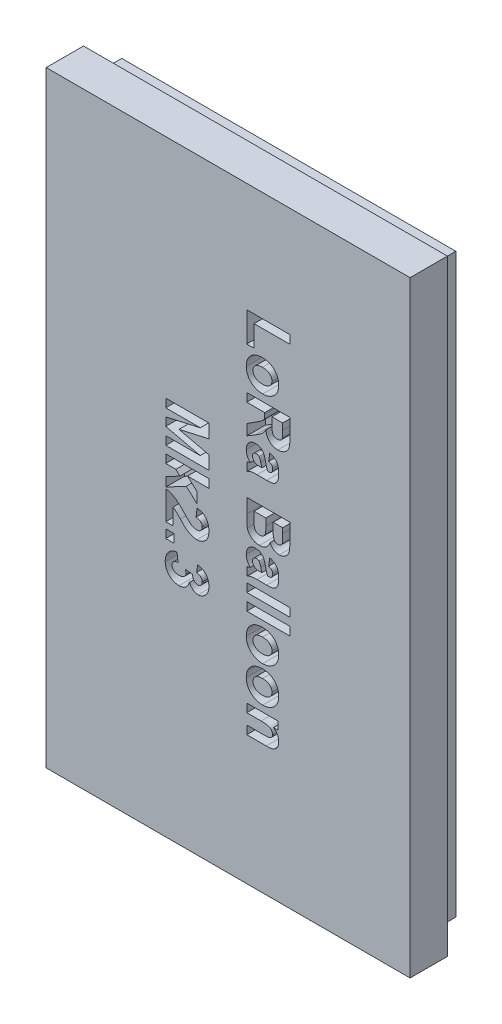
SolidWorks part; units mm, degrees
ref_plane "Front Plane" through (0, 0, 0) normal (0, 0, 1) x (1, 0, 0)
ref_plane "Top Plane" through (0, 0, 0) normal (0, 1, 0) x (1, 0, 0)
ref_plane "Right Plane" through (0, 0, 0) normal (1, 0, 0) x (0, 0, -1)
sketch "Sketch1" plane through (0, 0, 0) normal (0, 0, 1) x (1, 0, 0)
  line L1 (0, 0) -> (39, 0)
  line L2 (0, 0) -> (0, 65)
  line L3 (0, 65) -> (39, 65)
  line L4 (39, 0) -> (39, 65)
  dimension "D1" = 65
  dimension "D2" = 39
extrude "Base" add sketch "Sketch1" along normal blind 4
sketch "Sketch2" plane through (0, 0, 0) normal (0, 0, -1) x (-1, 0, 0)
  line L0 (-39, 0) -> (-39, 65) construction
  line L1 (-37.4, 63.4) -> (-35.6, 63.4)
  line L2 (-37.4, 63.4) -> (-37.4, 1.6)
  line L3 (-37.4, 1.6) -> (-35.6, 1.6)
  line L4 (-35.6, 63.4) -> (-35.6, 1.6)
  line L5 (0, 0) -> (-39, 0) construction
  line L6 (0, 65) -> (0, 0) construction
  line L7 (-35.6, 1.6) -> (-1.6, 1.6)
  line L8 (-35.6, 1.6) -> (-35.6, 3.4)
  line L9 (-35.6, 3.4) -> (-1.6, 3.4)
  line L10 (-1.6, 1.6) -> (-1.6, 3.4)
  line L12 (-39, 65) -> (0, 65) construction
  line L13 (-39, 32.5) -> (0, 32.5) construction
  line L14 (-19.5, 65) -> (-19.5, 0) construction
  line L15 (-35.6, 61.6) -> (-1.6, 61.6)
  line L16 (-1.6, 63.4) -> (-1.6, 61.6)
  line L17 (-35.6, 63.4) -> (-1.6, 63.4)
  line L18 (-35.6, 63.4) -> (-35.6, 61.6)
  line L19 (-1.6, 1.6) -> (-3.4, 1.6)
  line L20 (-3.4, 63.4) -> (-3.4, 1.6)
  line L21 (-1.6, 63.4) -> (-3.4, 63.4)
  line L22 (-1.6, 63.4) -> (-1.6, 1.6)
  dimension "D1" = 1.6
  dimension "D2" = 1.8
  dimension "D3" = 1.6
  dimension "D4" = 1.8
extrude "Mount" add sketch "Sketch2" along normal blind 2.5 contours L4 L1 L2 L3 | L22 L15 L20 L9 | L20 L9 L4 L7 | L9 L20 L7 L10 | L17 L20 L15 L16 | L20 L17 L4 L15 region at (36.5, 32.5, 0) region at (19.5, 62.5, 0) region at (2.5, 62.5, 0) region at (19.5, 2.5, 0) region at (2.5, 32.5, 0) region at (2.5, 2.5, 0)
sketch "Sketch3" plane through (0, 0, 4) normal (0, 0, 1) x (1, 0, 0)
  line L0 (21.5, 0) -> (21.5, 65) construction
  line L4 (0, 0) -> (39, 0) construction
  line L6 (0, 65) -> (0, 0) construction
  text T0 "<b>LoRa Balloon</b>\r\n<b>Mk2.3</b>" font "Arial Narrow" height in points 18
  dimension "D1" = 21.5
  dimension "D2" = 65
extrude "Logo" cut sketch "Sketch3" against normal blind 2
